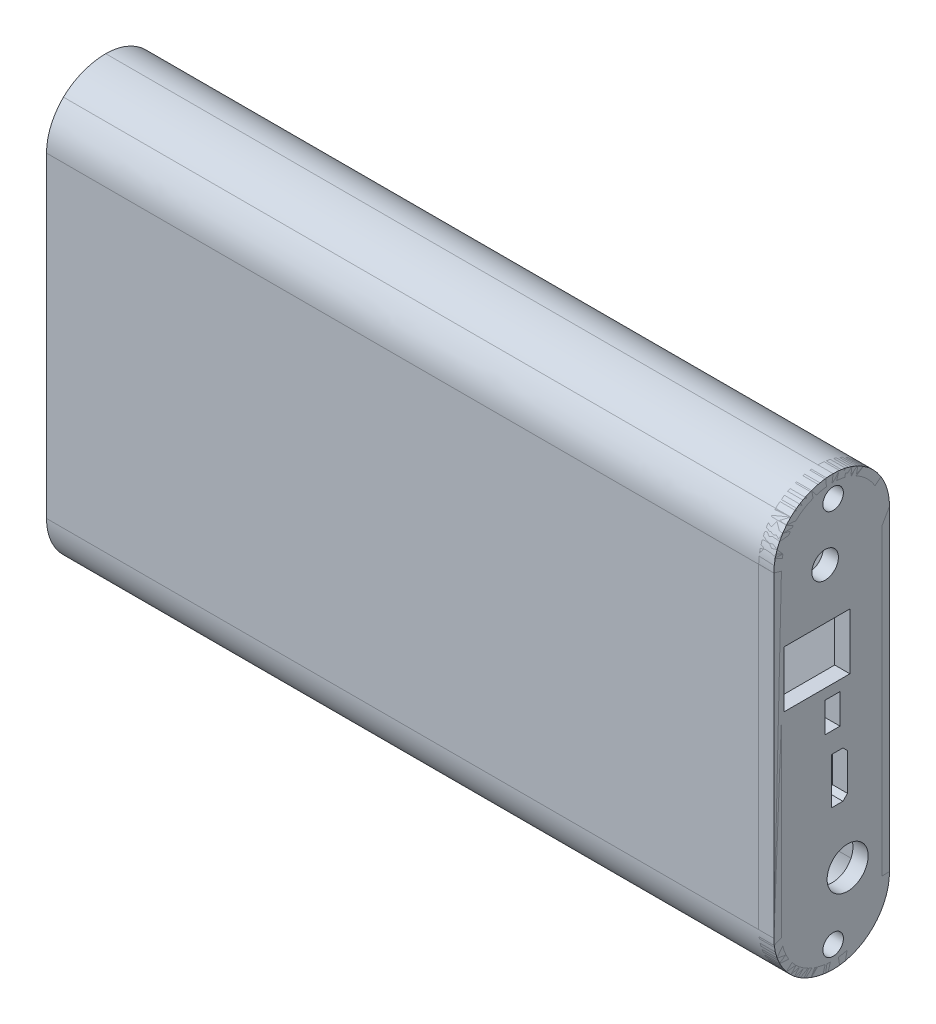
SolidWorks part; units mm, degrees
ref_plane "Front" through (0, 0, 0) normal (0, 0, 1) x (1, 0, 0)
ref_plane "Top" through (0, 0, 0) normal (0, 1, 0) x (1, 0, 0)
ref_plane "Right" through (0, 0, 0) normal (1, 0, 0) x (0, 0, -1)
sketch "Sketch1" plane through (0, 0, 0) normal (1, 0, 0) x (0, 0, -1)
  line L0 (0.0002, 71.7804) -> (0, 0) construction
  line L13 (0.0057, 68.1608) -> (-1.7087, 68.1608) construction
  line L14 (0.0057, 66.4464) -> (0.0057, 68.1608) construction
  line L15 (0.2716, 54.0701) -> (-2.9668, 54.0701) construction
  line L16 (0.2716, 50.8317) -> (0.2716, 54.0701) construction
  line L17 (0.2715, 41.3701) -> (-2.9669, 41.3701) construction
  line L18 (0.2715, 38.1317) -> (0.2715, 41.3701) construction
  line L19 (0.2715, 28.5051) -> (-2.9669, 28.5051) construction
  line L20 (0.2714, 25.2667) -> (0.2715, 28.5051) construction
  line L21 (-9.9007, 9.4411) -> (-9.9005, 62.3395)
  line L22 (9.4289, 62.3393) -> (9.4287, 9.4409)
  circle A8 centre (0.0057, 68.1608) radius 1.7144
  circle A9 centre (0.2716, 54.0701) radius 3.2384
  circle A10 centre (0.2715, 41.3701) radius 3.2384
  circle A11 centre (0.2715, 28.5051) radius 3.2384
  circle A12 centre (2.4304, 13.5437) radius 3.4289
  circle A13 centre (0.0053, 3.6195) radius 1.7144
  spline S35 degree 3 poles (-2.9668, 54.0701) (-2.9669, 55.8587) (-1.5169, 57.3086) (0.2715, 57.3086) knots 0.75 0.75 0.75 0.75 1 1 1 1 construction
  spline S36 degree 3 poles (0.2716, 50.8317) (-1.5169, 50.8316) (-2.9668, 52.2816) (-2.9668, 54.0701) knots 0.5 0.5 0.5 0.5 0.75 0.75 0.75 0.75 construction
  spline S37 degree 3 poles (3.51, 54.0702) (3.5101, 52.2816) (2.0601, 50.8317) (0.2716, 50.8317) knots 0.25 0.25 0.25 0.25 0.5 0.5 0.5 0.5 construction
  spline S38 degree 3 poles (0.2715, 57.3086) (2.0601, 57.3086) (3.51, 55.8587) (3.51, 54.0702) knots 0 0 0 0 0.25 0.25 0.25 0.25 construction
  spline S39 degree 3 poles (-2.9669, 41.3701) (-2.967, 43.1587) (-1.517, 44.6086) (0.2714, 44.6086) knots 0.75 0.75 0.75 0.75 1 1 1 1 construction
  spline S40 degree 3 poles (3.5099, 41.3702) (3.51, 39.5816) (2.06, 38.1317) (0.2715, 38.1317) knots 0.25 0.25 0.25 0.25 0.5 0.5 0.5 0.5 construction
  spline S41 degree 3 poles (0.2714, 44.6086) (2.06, 44.6086) (3.5099, 43.1587) (3.5099, 41.3702) knots 0 0 0 0 0.25 0.25 0.25 0.25 construction
  spline S42 degree 3 poles (-2.9669, 28.5051) (-2.967, 30.2937) (-1.517, 31.7436) (0.2714, 31.7436) knots 0.75 0.75 0.75 0.75 1 1 1 1 construction
  spline S43 degree 3 poles (0.2714, 25.2667) (-1.5171, 25.2666) (-2.967, 26.7166) (-2.9669, 28.5051) knots 0.5 0.5 0.5 0.5 0.75 0.75 0.75 0.75 construction
  spline S44 degree 3 poles (3.5099, 28.5052) (3.5099, 26.7166) (2.0599, 25.2667) (0.2714, 25.2667) knots 0.25 0.25 0.25 0.25 0.5 0.5 0.5 0.5 construction
  spline S45 degree 3 poles (-0.9985, 13.5437) (-0.9986, 15.4375) (0.5365, 16.9727) (2.4303, 16.9727) knots 0.75 0.75 0.75 0.75 1 1 1 1 construction
  spline S46 degree 3 poles (2.4304, 10.1148) (0.5366, 10.1147) (-0.9985, 11.65) (-0.9985, 13.5437) knots 0.5 0.5 0.5 0.5 0.75 0.75 0.75 0.75 construction
  spline S47 degree 3 poles (5.8593, 13.5438) (5.8594, 11.65) (4.3241, 10.1148) (2.4304, 10.1148) knots 0.25 0.25 0.25 0.25 0.5 0.5 0.5 0.5 construction
  spline S48 degree 3 poles (2.4303, 16.9727) (4.3241, 16.9727) (5.8593, 15.4375) (5.8593, 13.5438) knots 0 0 0 0 0.25 0.25 0.25 0.25 construction
  spline S49 degree 3 poles (0.0057, 66.4464) (0.9525, 66.4464) (1.7202, 67.214) (1.7201, 68.1609) knots 0.75 0.75 0.75 0.75 1 1 1 1 construction
  spline S50 degree 3 poles (-1.7087, 68.1608) (-1.7087, 67.214) (-0.9411, 66.4463) (0.0057, 66.4464) knots 0.5 0.5 0.5 0.5 0.75 0.75 0.75 0.75 construction
  spline S51 degree 3 poles (0.0057, 69.8753) (-0.9412, 69.8753) (-1.7088, 69.1077) (-1.7087, 68.1608) knots 0.25 0.25 0.25 0.25 0.5 0.5 0.5 0.5 construction
  spline S52 degree 3 poles (1.7201, 68.1609) (1.7201, 69.1077) (0.9525, 69.8753) (0.0057, 69.8753) knots 0 0 0 0 0.25 0.25 0.25 0.25 construction
  spline S53 degree 3 poles (0.0053, 1.9051) (0.9521, 1.9051) (1.7198, 2.6727) (1.7197, 3.6196) knots 0.75 0.75 0.75 0.75 1 1 1 1 construction
  spline S54 degree 3 poles (-1.7091, 3.6195) (-1.7091, 2.6727) (-0.9415, 1.905) (0.0053, 1.9051) knots 0.5 0.5 0.5 0.5 0.75 0.75 0.75 0.75 construction
  spline S55 degree 3 poles (0.0053, 5.334) (-0.9416, 5.334) (-1.7092, 4.5664) (-1.7091, 3.6195) knots 0.25 0.25 0.25 0.25 0.5 0.5 0.5 0.5 construction
  spline S56 degree 3 poles (1.7197, 3.6196) (1.7197, 4.5664) (0.9521, 5.334) (0.0053, 5.334) knots 0 0 0 0 0.25 0.25 0.25 0.25 construction
  spline S57 degree 3 poles (0.2666, 38.1317) (-1.5219, 38.1316) (-2.9718, 39.5816) (-2.9718, 41.3701) knots 0.5 0.5 0.5 0.5 0.75 0.75 0.75 0.75 construction
  spline S58 degree 3 poles (0.0053, 1.9051) (0.9521, 1.9051) (1.7198, 2.6727) (1.7197, 3.6196) knots 0.75 0.75 0.75 0.75 1 1 1 1 construction
  spline S59 degree 3 poles (-1.7091, 3.6195) (-1.7091, 2.6727) (-0.9415, 1.905) (0.0053, 1.9051) knots 0.5 0.5 0.5 0.5 0.75 0.75 0.75 0.75 construction
  spline S60 degree 3 poles (0.0053, 5.334) (-0.9416, 5.334) (-1.7092, 4.5664) (-1.7091, 3.6195) knots 0.25 0.25 0.25 0.25 0.5 0.5 0.5 0.5 construction
  spline S61 degree 3 poles (1.7197, 3.6196) (1.7197, 4.5664) (0.9521, 5.334) (0.0053, 5.334) knots 0 0 0 0 0.25 0.25 0.25 0.25 construction
  spline S62 degree 3 poles (-7.0656, 69.0205) (-5.24, 70.8008) (-2.5466, 71.782) (0.0002, 71.7804) knots 0.9 0.9 0.9 0.9 1 1 1 1
  spline S63 degree 3 poles (-9.9005, 62.3395) (-9.8988, 64.8571) (-8.8676, 67.2635) (-7.0656, 69.0205) knots 0.8 0.8 0.8 0.8 0.9 0.9 0.9 0.9
  spline S64 degree 3 poles (-7.0749, 2.7684) (-8.8738, 4.5268) (-9.9024, 6.9231) (-9.9007, 9.4411) knots 0.6 0.6 0.6 0.6 0.7 0.7 0.7 0.7
  spline S65 degree 3 poles (0, 0) (-2.5473, 0.0015) (-5.2522, 0.9866) (-7.0749, 2.7684) knots 0.5 0.5 0.5 0.5 0.6 0.6 0.6 0.6
  spline S66 degree 3 poles (6.6645, 2.7592) (4.897, 0.9915) (2.4997, -0.0016) (0, 0) knots 0.4 0.4 0.4 0.4 0.5 0.5 0.5 0.5
  spline S67 degree 3 poles (9.4287, 9.4409) (9.427, 6.9399) (8.4336, 4.5283) (6.6645, 2.7592) knots 0.3 0.3 0.3 0.3 0.4 0.4 0.4 0.4
  spline S68 degree 3 poles (6.6733, 69.0128) (8.4398, 67.2418) (9.4306, 64.8407) (9.4289, 62.3393) knots 0.1 0.1 0.1 0.1 0.2 0.2 0.2 0.2
  spline S69 degree 3 poles (0.0002, 71.7804) (2.4996, 71.7789) (4.9078, 70.7829) (6.6733, 69.0128) knots 0 0 0 0 0.1 0.1 0.1 0.1
  point P116 (2.4304, 13.5437)
  point P117 (0.2715, 28.5051)
extrude "Boss-Extrude1" add sketch "Sketch1" along normal blind 121.6 contours L22 S67 S66 S65 S64 L21 S63 S62 S69 S68
shell "Shell1" thickness 1.27 removed face at (121.6, 35.8902, 0.1746) removed face at (0, 35.8902, 0.1746)
extrude "Boss-Extrude2" add sketch "Sketch1<3>" along normal blind 2.54
sketch "Sketch1<3>" plane through (0, 0, 0) normal (1, 0, 0) x (0, 0, -1) same geometry as "Sketch1"
sketch "Sketch3" plane through (121.6, 0, 0) normal (1, 0, 0) x (0, 0, -1)
  line L0 (2.7173, 50.7002) -> (-8.1246, 41.488) construction
  line L1 (0.0055, 69.8753) -> (0.0055, 68.1609) construction
  line L2 (2.8081, 50.7931) -> (2.8081, 41.3951)
  line L3 (2.8081, 50.7931) -> (-8.2154, 50.7931)
  line L4 (-8.2154, 50.7931) -> (-8.2154, 41.3951)
  line L5 (2.8081, 41.3951) -> (-8.2154, 41.3951)
  line L6 (2.8081, 50.7931) -> (-8.2154, 41.3951) construction
  line L7 (-8.2154, 50.7931) -> (2.8081, 41.3951) construction
  line L8 (0.0055, 68.1609) -> (-1.7089, 68.1609) construction
  line L9 (-1.332, 61.4676) -> (-1.332, 59.2451) construction
  line L10 (-1.332, 59.2451) -> (-3.5546, 59.2451) construction
  line L11 (2.4271, 16.9539) -> (2.4271, 13.525) construction
  line L12 (2.4271, 13.525) -> (-1.0018, 13.525) construction
  line L13 (0.0055, 5.334) -> (0.0055, 3.6196) construction
  line L14 (0.0055, 3.6196) -> (-1.7089, 3.6196) construction
  line L15 (1.6443, 31.2465) -> (2.4063, 30.4845)
  line L16 (1.157, 39.6488) -> (1.157, 34.6451)
  line L17 (1.157, 39.6488) -> (-1.3321, 39.6488)
  line L18 (-1.3321, 39.6488) -> (-1.3321, 34.6451)
  line L19 (1.157, 34.6451) -> (-1.3321, 34.6451)
  line L20 (-0.2353, 31.2465) -> (-0.2353, 23.5249)
  line L21 (-0.2353, 31.2465) -> (1.6443, 31.2465)
  line L22 (2.4063, 30.4845) -> (2.4063, 24.2869)
  line L23 (-0.2353, 23.5249) -> (1.6443, 23.5249)
  line L24 (2.4063, 24.2869) -> (1.6443, 23.5249)
  line L25 (1.6648, 31.2465) -> (-0.2353, 31.2465) construction
  line L26 (-0.2353, 31.2465) -> (-0.2353, 23.5249) construction
  line L27 (-0.2353, 23.5249) -> (1.6648, 23.5249) construction
  line L28 (1.6648, 23.5249) -> (2.4063, 24.3118) construction
  line L29 (2.4063, 24.3118) -> (2.4063, 30.4596) construction
  line L30 (2.4063, 30.4596) -> (1.6648, 31.2465) construction
  line L31 (2.4984, 41.3951) -> (-7.9058, 41.3951) construction
  line L32 (-8.2155, 41.7126) -> (-8.2155, 50.4756) construction
  line L33 (-7.9058, 50.7931) -> (2.4984, 50.7931) construction
  line L34 (2.8081, 50.4756) -> (2.8081, 41.7126) construction
  line L35 (1.157, 34.6451) -> (-1.3321, 34.6451) construction
  line L36 (-1.3321, 34.6451) -> (-1.3321, 39.6488) construction
  line L37 (-1.3321, 39.6488) -> (1.157, 39.6488) construction
  line L38 (1.157, 39.6488) -> (1.157, 34.6451) construction
  line L43 (-9.9005, 62.3395) -> (-9.9007, 9.4411)
  line L44 (9.4287, 9.4409) -> (9.4289, 62.3393)
  line L47 (-9.9005, 62.3395) -> (-9.9007, 9.4411)
  line L48 (9.4287, 9.4409) -> (9.4289, 62.3393)
  circle A0 centre (2.4271, 13.525) radius 3.4289
  circle A1 centre (0.0055, 3.6196) radius 1.7144
  circle A2 centre (-1.332, 59.2451) radius 2.2226
  circle A3 centre (0.0055, 68.1609) radius 1.7144
  spline S0 degree 3 poles (1.7199, 68.1608) (1.7199, 67.214) (0.9523, 66.4464) (0.0055, 66.4464) knots 0 0 0 0 0.25 0.25 0.25 0.25 construction
  spline S1 degree 3 poles (0.0055, 66.4464) (-0.9414, 66.4464) (-1.709, 67.214) (-1.7089, 68.1609) knots 0.25 0.25 0.25 0.25 0.5 0.5 0.5 0.5 construction
  spline S2 degree 3 poles (-1.7089, 68.1609) (-1.7089, 69.1077) (-0.9413, 69.8754) (0.0055, 69.8753) knots 0.5 0.5 0.5 0.5 0.75 0.75 0.75 0.75 construction
  spline S3 degree 3 poles (0.0055, 69.8753) (0.9523, 69.8753) (1.72, 69.1077) (1.7199, 68.1608) knots 0.75 0.75 0.75 0.75 1 1 1 1 construction
  spline S4 degree 3 poles (0.8904, 59.245) (0.8904, 58.0176) (-0.1046, 57.0224) (-1.3321, 57.0226) knots 0 0 0 0 0.25 0.25 0.25 0.25 construction
  spline S5 degree 3 poles (-1.3321, 57.0226) (-2.5595, 57.0226) (-3.5547, 58.0176) (-3.5546, 59.2451) knots 0.25 0.25 0.25 0.25 0.5 0.5 0.5 0.5 construction
  spline S6 degree 3 poles (-3.5546, 59.2451) (-3.5546, 60.4725) (-2.5595, 61.4677) (-1.332, 61.4676) knots 0.5 0.5 0.5 0.5 0.75 0.75 0.75 0.75 construction
  spline S7 degree 3 poles (-1.332, 61.4676) (-0.1046, 61.4676) (0.8905, 60.4725) (0.8904, 59.245) knots 0.75 0.75 0.75 0.75 1 1 1 1 construction
  spline S8 degree 3 poles (-7.9058, 41.3951) (-7.988, 41.395) (-8.0664, 41.4284) (-8.1246, 41.488) knots 0.083333 0.083333 0.083333 0.083333 0.166667 0.166667 0.166667 0.166667 construction
  spline S9 degree 3 poles (-8.1246, 41.488) (-8.1827, 41.5475) (-8.2154, 41.6283) (-8.2155, 41.7126) knots 0.166667 0.166667 0.166667 0.166667 0.25 0.25 0.25 0.25 construction
  spline S10 degree 3 poles (-8.2155, 50.4756) (-8.2155, 50.5598) (-8.1829, 50.6403) (-8.1248, 50.6999) knots 0.333333 0.333333 0.333333 0.333333 0.416667 0.416667 0.416667 0.416667 construction
  spline S11 degree 3 poles (-8.1248, 50.6999) (-8.0668, 50.7595) (-7.988, 50.793) (-7.9058, 50.7931) knots 0.416667 0.416667 0.416667 0.416667 0.5 0.5 0.5 0.5 construction
  spline S12 degree 3 poles (2.4984, 50.7931) (2.5807, 50.7931) (2.6591, 50.7597) (2.7173, 50.7002) knots 0.583333 0.583333 0.583333 0.583333 0.666667 0.666667 0.666667 0.666667 construction
  spline S13 degree 3 poles (2.7173, 50.7002) (2.7754, 50.6406) (2.8081, 50.5598) (2.8081, 50.4756) knots 0.666667 0.666667 0.666667 0.666667 0.75 0.75 0.75 0.75 construction
  spline S14 degree 3 poles (2.8081, 41.7126) (2.8082, 41.6283) (2.7756, 41.5479) (2.7175, 41.4883) knots 0.833333 0.833333 0.833333 0.833333 0.916667 0.916667 0.916667 0.916667 construction
  spline S15 degree 3 poles (2.7175, 41.4883) (2.6595, 41.4287) (2.5807, 41.3951) (2.4984, 41.3951) knots 0.916667 0.916667 0.916667 0.916667 1 1 1 1 construction
  spline S16 degree 3 poles (1.7199, 3.6195) (1.7199, 2.6727) (0.9523, 1.9051) (0.0055, 1.9051) knots 0 0 0 0 0.25 0.25 0.25 0.25 construction
  spline S17 degree 3 poles (0.0055, 1.9051) (-0.9414, 1.9051) (-1.709, 2.6727) (-1.7089, 3.6196) knots 0.25 0.25 0.25 0.25 0.5 0.5 0.5 0.5 construction
  spline S18 degree 3 poles (-1.7089, 3.6196) (-1.7089, 4.5664) (-0.9413, 5.3341) (0.0055, 5.334) knots 0.5 0.5 0.5 0.5 0.75 0.75 0.75 0.75 construction
  spline S19 degree 3 poles (0.0055, 5.334) (0.9523, 5.334) (1.72, 4.5664) (1.7199, 3.6195) knots 0.75 0.75 0.75 0.75 1 1 1 1 construction
  spline S20 degree 3 poles (5.856, 13.5249) (5.856, 11.6312) (4.3208, 10.096) (2.427, 10.096) knots 0 0 0 0 0.25 0.25 0.25 0.25 construction
  spline S21 degree 3 poles (2.427, 10.096) (0.5332, 10.096) (-1.0019, 11.6312) (-1.0018, 13.525) knots 0.25 0.25 0.25 0.25 0.5 0.5 0.5 0.5 construction
  spline S22 degree 3 poles (-1.0018, 13.525) (-1.0018, 15.4187) (0.5333, 16.954) (2.4271, 16.9539) knots 0.5 0.5 0.5 0.5 0.75 0.75 0.75 0.75 construction
  spline S23 degree 3 poles (2.4271, 16.9539) (4.3208, 16.9539) (5.8561, 15.4187) (5.856, 13.5249) knots 0.75 0.75 0.75 0.75 1 1 1 1 construction
  spline S33 degree 3 poles (-1871.1484, 2381.7643) (1420.5919, -2625.3922) (-870.8349, 2975.0469) (291.7142, -2903.4303) knots -1.584474 -1.584474 -1.584474 -1.584474 1.883369 1.883369 1.883369 1.883369 only from (9.4289, 62.3393) to (6.6733, 69.0128)
  spline S34 degree 3 poles (-2966.6945, 350.5285) (2921.6127, -792.2321) (-2706.0073, 1456.4754) (2347.6234, -1774.3139) knots -1.66141 -1.66141 -1.66141 -1.66141 1.765619 1.765619 1.765619 1.765619 only from (6.6733, 69.0128) to (0.0002, 71.7804)
  spline S35 degree 3 poles (-2788.2853, -1018.3189) (2996.8749, 813.2517) (-3068.9943, -288.7053) (2985.8479, 16.7691) knots -0.504234 -0.504234 -0.504234 -0.504234 2.365423 2.365423 2.365423 2.365423 only from (0.0002, 71.7804) to (-7.0656, 69.0205)
  spline S36 degree 3 poles (-473.6707, -2880.3042) (1045.7459, 2917.3717) (-1577.8393, -2537.4254) (1998.6373, 2272.4065) knots -0.867322 -0.867322 -0.867322 -0.867322 2.551632 2.551632 2.551632 2.551632 only from (-7.0656, 69.0205) to (-9.9005, 62.3395)
  spline S37 degree 3 poles (2051.2221, -2151.1789) (-1629.2539, 2573.0935) (1091.6811, -2824.4203) (-508.9293, 2945.7069) knots -1.066452 -1.066452 -1.066452 -1.066452 2.388996 2.388996 2.388996 2.388996 only from (-9.9007, 9.4411) to (-7.0749, 2.7684)
  spline S38 degree 3 poles (2986.1112, 49.3188) (-3070.0305, 360.0249) (2999.5395, -734.732) (-2793.5615, 1077.0043) knots -0.854143 -0.854143 -0.854143 -0.854143 1.992615 1.992615 1.992615 1.992615 only from (-7.0749, 2.7684) to (0, 0)
  spline S39 degree 3 poles (2305.4815, 1897.5759) (-2676.9912, -1430.1394) (2906.1332, 899.9316) (-2963.784, -301.112) knots -1.284054 -1.284054 -1.284054 -1.284054 2.185043 2.185043 2.185043 2.185043 only from (0, 0) to (6.6645, 2.7592)
  spline S40 degree 3 poles (266.0829, 2978.1993) (-832.002, -2919.1639) (1372.6775, 2726.9145) (-1817.7243, -2353.0652) knots -1.360264 -1.360264 -1.360264 -1.360264 2.066759 2.066759 2.066759 2.066759 only from (6.6645, 2.7592) to (9.4287, 9.4409)
  spline S41 degree 3 poles (9.4289, 62.3393) (9.4306, 64.8407) (8.4398, 67.2418) (6.6733, 69.0128) knots 0.1 0.1 0.1 0.1 0.2 0.2 0.2 0.2
  spline S42 degree 3 poles (6.6733, 69.0128) (4.9078, 70.7829) (2.4996, 71.7789) (0.0002, 71.7804) knots 0 0 0 0 0.1 0.1 0.1 0.1
  spline S43 degree 3 poles (0.0002, 71.7804) (-2.5466, 71.782) (-5.24, 70.8008) (-7.0656, 69.0205) knots 0.9 0.9 0.9 0.9 1 1 1 1
  spline S44 degree 3 poles (-7.0656, 69.0205) (-8.8676, 67.2635) (-9.8988, 64.8571) (-9.9005, 62.3395) knots 0.8 0.8 0.8 0.8 0.9 0.9 0.9 0.9
  spline S45 degree 3 poles (-9.9007, 9.4411) (-9.9024, 6.9231) (-8.8738, 4.5268) (-7.0749, 2.7684) knots 0.6 0.6 0.6 0.6 0.7 0.7 0.7 0.7
  spline S46 degree 3 poles (-7.0749, 2.7684) (-5.2522, 0.9866) (-2.5473, 0.0015) (0, 0) knots 0.5 0.5 0.5 0.5 0.6 0.6 0.6 0.6
  spline S47 degree 3 poles (0, 0) (2.4997, -0.0016) (4.897, 0.9915) (6.6645, 2.7592) knots 0.4 0.4 0.4 0.4 0.5 0.5 0.5 0.5
  spline S48 degree 3 poles (6.6645, 2.7592) (8.4336, 4.5283) (9.427, 6.9399) (9.4287, 9.4409) knots 0.3 0.3 0.3 0.3 0.4 0.4 0.4 0.4
  point P0 (-2.7036, 46.0941)
  point P9 (2.4063, 23.5249)
  point P10 (2.4063, 31.2465)
  dimension "D1" = 0.762
  dimension "D2" = 0.762
  dimension "D3" = 0.762
  dimension "D4" = 0.762
  dimension "D5" = 0
extrude "Boss-Extrude3" add sketch "Sketch3" against normal blind 2.54
